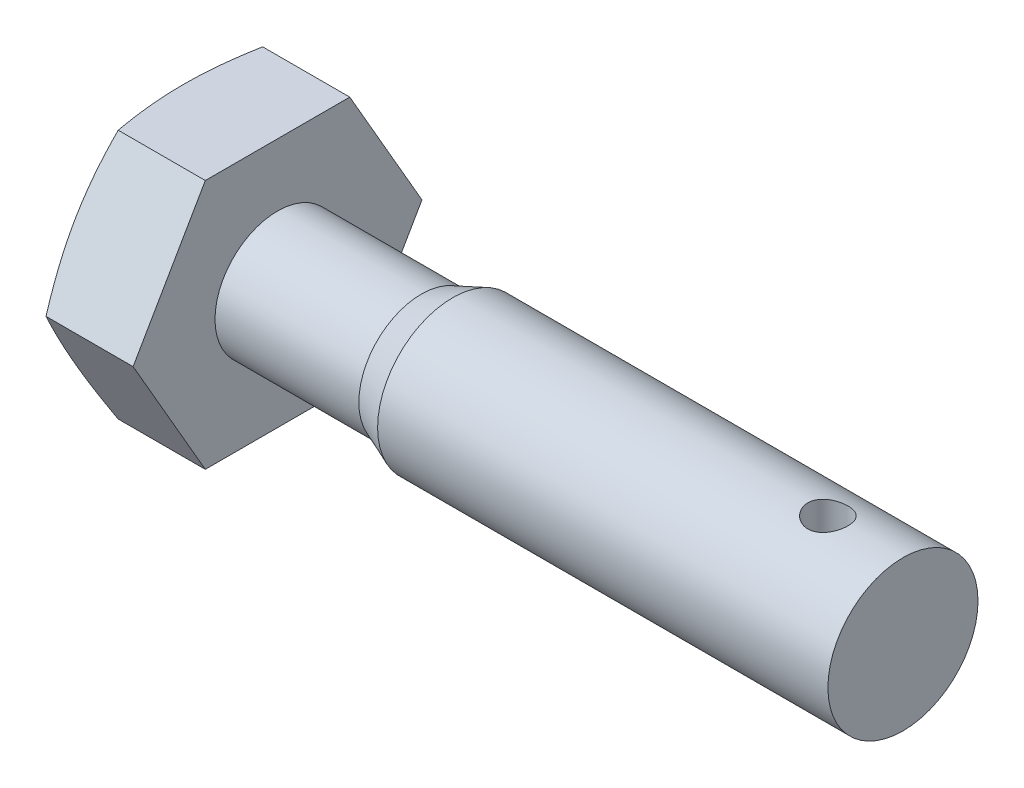
SolidWorks part; units mm, degrees
ref_plane "Front" through (0, 0, 0) normal (0, 0, 1) x (1, 0, 0)
ref_plane "Top" through (0, 0, 0) normal (0, 1, 0) x (1, 0, 0)
ref_plane "Right" through (0, 0, 0) normal (1, 0, 0) x (0, 0, -1)
sketch "Sketch1" plane through (0, 0, 0) normal (1, 0, 0) x (0, 0, -1)
  line L1 (2.8868, -5) -> (5.7735, 0)
  line L2 (5.7735, 0) -> (2.8868, 5)
  line L3 (2.8868, 5) -> (-2.8868, 5)
  line L4 (-2.8868, 5) -> (-5.7735, 0)
  line L5 (-5.7735, 0) -> (-2.8868, -5)
  line L6 (-2.8868, -5) -> (2.8868, -5)
  circle A0 centre (0, 0) radius 5 construction
  dimension "s" = 10
extrude "BaseHead" add sketch "Sketch1" along normal blind 4
ref_plane "Plane1" through (11, 0, 0) normal (1, 0, 0) x (0, 0, -1)
sketch "Sketch2" plane through (4, 0, 0) normal (1, 0, 0) x (0, 0, -1)
  circle A0 centre (0, 0) radius 3
extrude "BaseBody" add sketch "Sketch2" along normal blind 25
cosmetic thread "ThreadCosmetic1" [suppressed] parameters "b"=18, "D2"=4.92
sketch "Sketch3" plane through (3.1612, 0, 2.6123) normal (0, 1, 0) x (0, 0, -1)
  line L0 (2.6123, 2.0714) -> (2.6123, -1.5224) construction
  line L2 (8.3858, 3.1612) -> (8.3858, 2.6431)
  line L3 (8.3858, 2.6431) -> (6.9623, 3.1612)
  line L5 (6.9623, 3.1612) -> (8.3858, 3.1612)
  dimension "D1" = 20
  dimension "dw" = 8.7
revolve "HeadChamfer" cut sketch "Sketch3" angle 360 about L0
sketch "Sketch4" plane through (0, 0, 0) normal (1, 0, 0) x (0, 0, -1)
  circle A0 centre (0, 0) radius 3.4
  dimension "da" = 6.8
extrude "Cut-Extrude1" cut sketch "Sketch4" along normal blind 0.8
sketch "Sketch5" plane through (-2.9296, 0, 7.9296) normal (0, 1, 0) x (0, 0, -1)
  line L0 (7.9296, -2.9296) -> (7.9296, -19.1832) construction
  line L1 (13.7031, -6.9296) -> (10.8164, -6.9296) construction
  line L2 (10.9296, -13.9296) -> (10.4296, -12.6796)
  line L3 (10.9296, -2.9296) -> (10.9296, -19.1832) construction
  line L4 (10.4296, -12.6796) -> (10.4296, -6.9296)
  line L5 (10.9296, -31.9296) -> (10.9296, -6.9296) construction
  line L6 (10.4296, -6.9296) -> (12.9296, -6.9296)
  line L7 (12.9296, -6.9296) -> (12.9296, -13.9296)
  line L8 (12.9296, -13.9296) -> (10.9296, -13.9296)
  line L9 (4.9296, -31.9296) -> (10.9296, -31.9296) construction
  dimension "D4" = 10
  dimension "D3" = 18
revolve "Cut-Revolve1" cut sketch "Sketch5" angle 360 about L0
fillet "HeadFillet" [suppressed] radius 0.25
sketch "Sketch6" plane through (0, 0, 0) normal (0, 1, 0) x (1, 0, 0)
  line L0 (4, -2.8868) -> (4, -5.7735) construction
  circle A0 centre (26, 0) radius 0.8
  dimension "d1" = 1.6
  dimension "lh" = 22
extrude "Hole" cut sketch "Sketch6" against normal through all and the other way through all
sketch "Sketch7" plane through (0, 0, 0) normal (0, 0, 1) x (1, 0, 0)
  line L0 (28.73, 3.2) -> (29.27, 3.2)
  line L1 (29.27, 3.2) -> (29.27, 3)
  line L2 (29.27, 3) -> (29, 2.5323)
  line L3 (28.73, 3) -> (29, 2.5323)
  line L4 (28.73, 3.2) -> (28.73, 3)
  line L5 (29.0273, 0) -> (0, 0) construction
  line L6 (28.73, 3) -> (29.27, 3) construction
  line L7 (29, 3) -> (29, 2.5323) construction
  line L8 (29, -3) -> (29, 3) construction
  line L9 (29, 3) -> (26.8, 3) construction
  point P5 (29, 3.2)
  dimension "D1" = 0.2
  dimension "D2" = 0.54
revolve "Cut-Revolve10" [suppressed] cut sketch "Sketch7" angle 360 about L5
pattern_linear "LPattern10" [suppressed] count 28 spacing 0.648 along (-1, 0, 0) of bodies 110
equation "\"D1@Cut-Extrude1\" = 0.2 * \"k@BaseHead\""
equation "\"b@ThreadCosmetic1\" = \"l@BaseBody\" - \"lg@Plane1\""
equation "\"D4@Sketch5\" = 2 * \"ds@Sketch5\""
equation "\"D3@Sketch5\" = \"l@BaseBody\" - \"lg@Plane1\""
equation "\"D2@Sketch7\" = (  \"d@Sketch2\" - \"D2@ThreadCosmetic1\" )  / 2"
equation "\"D3@LPattern10\" = \"D2@Sketch7\" * 1.2"
equation "\"D1@LPattern10\" = \"b@ThreadCosmetic1\" / \"D3@LPattern10\""
